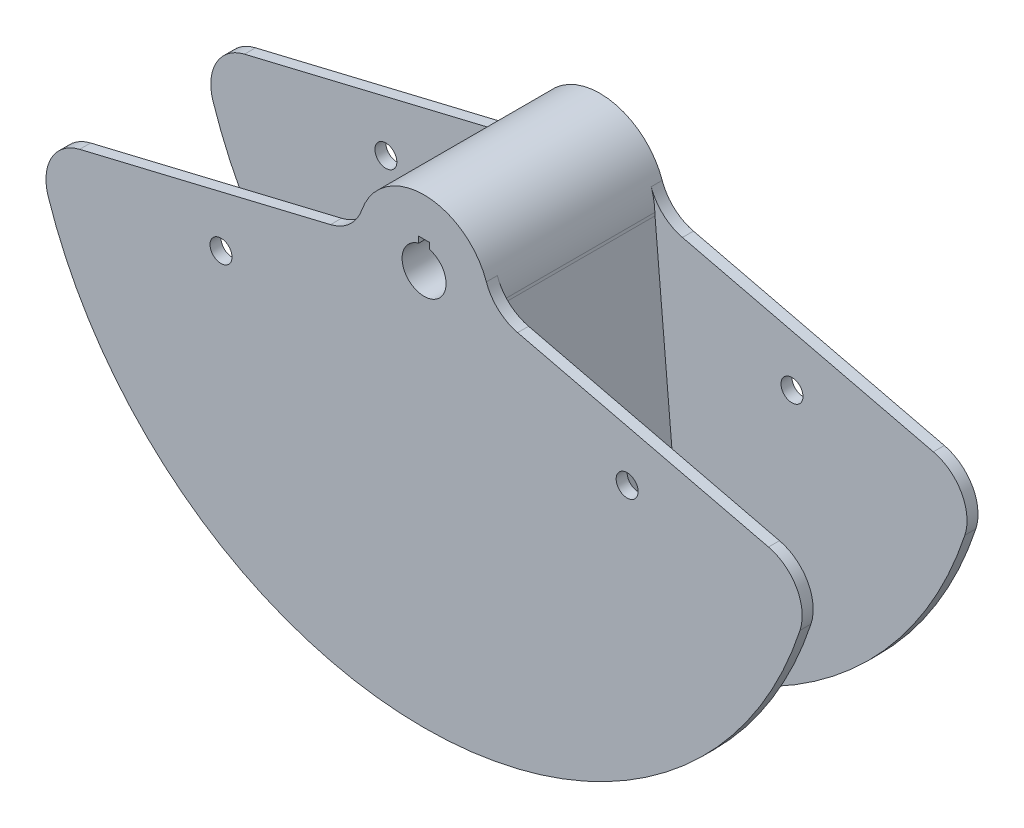
SolidWorks part; units mm, degrees
material "AISI 1020"
ref_plane "Front Plane" through (0, 0, 0) normal (0, 0, 1) x (1, 0, 0)
ref_plane "Top Plane" through (0, 0, 0) normal (0, 1, 0) x (1, 0, 0)
ref_plane "Right Plane" through (0, 0, 0) normal (1, 0, 0) x (0, 0, -1)
other "Center of Mass"
sketch "Sketch1" plane through (0, 0, 0) normal (0, 0, 1) x (1, 0, 0)
  line L0 (-57.4579, -221.2613) -> (-38.1844, -0.9642)
  line L1 (-38.1, 0) -> (38.1, 0) construction
  line L2 (38.1844, -0.9642) -> (57.4579, -221.2613)
  line L3 (0, 0) -> (-117.3327, -48.6008) construction
  line L4 (0, 0) -> (0, -228.6) construction
  line L5 (117.3327, -48.6008) -> (0, 0) construction
  arc A0 (-57.4579, -221.2613) -> (57.4579, -221.2613) centre (0, 0) ccw
  circle A1 centre (0, 0) radius 127 construction
  circle A2 centre (0, 0) radius 12.7
  arc A3 (38.0926, 0.7497) -> (-38.0926, 0.7497) centre (0, 0) ccw
  circle A4 centre (-117.3327, -48.6008) radius 12.7 construction
  circle A5 centre (117.3327, -48.6008) radius 12.7 construction
  arc A6 (38.1844, -0.9642) -> (38.0926, 0.7497) centre (63.4877, 1.2495) cw
  arc A7 (-38.1844, -0.9642) -> (-38.0926, 0.7497) centre (-63.4877, 1.2495) ccw
  dimension "D1" = 457.2
  dimension "D2" = 254
  dimension "D3" = 25.4
  dimension "D4" = 25.4
  dimension "D5" = 25.4
  dimension "D8" = 25.4
  dimension "D6" = 135
  dimension "D7" = 67.5
  dimension "D9" = 10
extrude "Boss-Extrude1" add sketch "Sketch1" along normal mid plane 88.9
sketch "Sketch5" plane through (0, 0, 44.45) normal (0, 0, 1) x (1, 0, 0)
  line L0 (-199.009, -38.6308) -> (-54.0427, -3.8275)
  line L1 (-38.1, 0) -> (38.1, 0) construction
  line L2 (54.0427, -3.8275) -> (199.009, -38.6308)
  line L3 (0, 0) -> (-117.3327, -48.6008) construction
  line L4 (0, 0) -> (0, -228.6) construction
  line L5 (117.3327, -48.6008) -> (0, 0) construction
  line L6 (-117.3327, -48.6008) -> (117.3327, -48.6008) construction
  arc A0 (-217.2144, -71.2451) -> (217.2144, -71.2451) centre (0, 0) ccw
  circle A2 centre (0, 0) radius 12.7
  arc A3 (35.9833, 12.5224) -> (-35.9833, 12.5224) centre (0, 0) ccw
  circle A4 centre (-117.3327, -48.6008) radius 6.35
  circle A5 centre (117.3327, -48.6008) radius 6.35
  arc A6 (54.0427, -3.8275) -> (35.9833, 12.5224) centre (59.9722, 20.8707) cw
  arc A7 (-54.0427, -3.8275) -> (-35.9833, 12.5224) centre (-59.9722, 20.8707) ccw
  arc A8 (-199.009, -38.6308) -> (-217.2144, -71.2451) centre (-193.0795, -63.329) ccw
  arc A9 (199.009, -38.6308) -> (217.2144, -71.2451) centre (193.0795, -63.329) cw
  dimension "D1" = 457.2
  dimension "D2" = 153
  dimension "D3" = 25.4
  dimension "D5" = 12.7
  dimension "D8" = 25.4
  dimension "D4" = 25.4
  dimension "D10" = 25.4
  dimension "D6" = 135
  dimension "D9" = 127
extrude "Boss-Extrude2" add sketch "Sketch5" along normal blind 6.35
sketch "Sketch6" plane through (0, 0, -44.45) normal (0, 0, -1) x (-1, 0, 0)
  line L0 (-222.4045, -51.6882) -> (-53.3494, -4.2767)
  line L1 (-38.1, 0) -> (38.1, 0) construction
  line L2 (53.3494, -4.2767) -> (222.4045, -51.6882)
  line L3 (0, 0) -> (-117.3327, -48.6008) construction
  line L4 (0, 0) -> (0, -254) construction
  line L5 (117.3327, -48.6008) -> (0, 0) construction
  arc A0 (-239.4952, -84.6052) -> (239.4952, -84.6052) centre (0, 0) ccw
  circle A1 centre (0, 0) radius 127 construction
  circle A2 centre (0, 0) radius 12.7
  arc A3 (36.1249, 12.1078) -> (-36.1249, 12.1078) centre (0, 0) ccw
  circle A4 centre (-117.3327, -48.6008) radius 6.35
  circle A5 centre (117.3327, -48.6008) radius 6.35
  arc A6 (53.3494, -4.2767) -> (36.1249, 12.1078) centre (60.2082, 20.1797) cw
  arc A7 (-53.3494, -4.2767) -> (-36.1249, 12.1078) centre (-60.2082, 20.1797) ccw
  arc A8 (222.4045, -51.6882) -> (239.4952, -84.6052) centre (215.5457, -76.1446) cw
  arc A9 (-222.4045, -51.6882) -> (-239.4952, -84.6052) centre (-215.5457, -76.1446) ccw
  dimension "D1" = 508
  dimension "D2" = 254
  dimension "D3" = 25.4
  dimension "D4" = 12.7
  dimension "D7" = 25.4
  dimension "D9" = 25.4
  dimension "D10" = 25.4
  dimension "D5" = 135
  dimension "D6" = 67.5
  dimension "D8" = 25.4
extrude "Boss-Extrude4" [suppressed] add sketch "Sketch6" along normal blind 6.35
mirror "Mirror1" about plane through (0, 0, 0) normal (0, 0, 1) of "Boss-Extrude2"
sketch "Sketch8" plane through (0, 0, 0) normal (0, 0, 1) x (1, 0, 0)
  line L0 (0, 0) -> (0, 12.7) construction
  line L2 (3.175, 9.525) -> (-3.175, 9.525)
  line L3 (3.175, 9.525) -> (3.175, 15.875)
  line L4 (3.175, 15.875) -> (-3.175, 15.875)
  line L5 (-3.175, 9.525) -> (-3.175, 15.875)
  line L6 (3.175, 9.525) -> (-3.175, 15.875) construction
  line L7 (3.175, 15.875) -> (-3.175, 9.525) construction
  circle A0 centre (0, 0) radius 12.7 construction
  arc A1 (3.175, 12.2967) -> (-3.175, 12.2967) centre (0, 0) ccw
  dimension "D1" = 6.35
  dimension "D2" = 6.35
extrude "Cut-Extrude1" cut sketch "Sketch8" against normal through all both and the other way through all contours L3 L4 L5 L2
